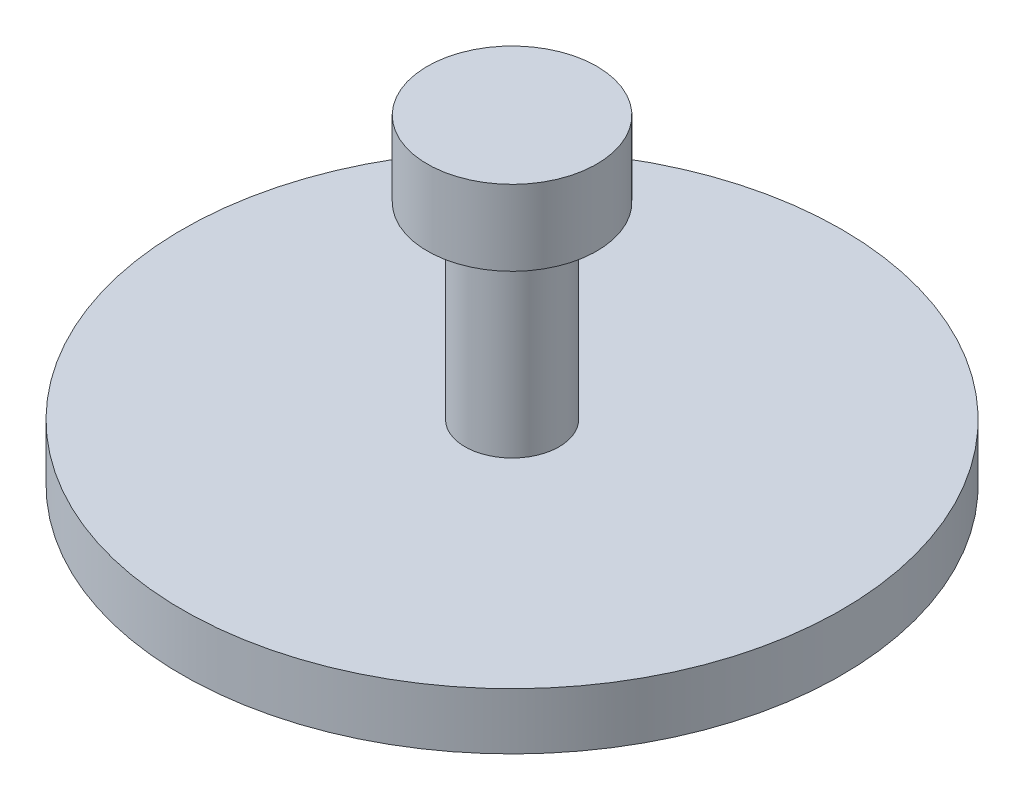
SolidWorks part; units mm, degrees
material "Plain Carbon Steel"
ref_plane "Front Plane" through (0, 0, 0) normal (0, 0, 1) x (1, 0, 0)
ref_plane "Top Plane" through (0, 0, 0) normal (0, 1, 0) x (1, 0, 0)
ref_plane "Right Plane" through (0, 0, 0) normal (1, 0, 0) x (0, 0, -1)
sketch "Sketch1" plane through (0, 0, 0) normal (0, 0, 1) x (1, 0, 0)
  line L0 (0, 0) -> (0, 17) construction
  line L1 (0, 0) -> (17.5, 0)
  line L2 (17.5, 0) -> (17.5, 3)
  line L3 (17.5, 3) -> (2.5, 3)
  line L4 (2.5, 3) -> (2.5, 13)
  line L5 (2.5, 13) -> (4.5, 13)
  line L6 (4.5, 13) -> (4.5, 17)
  line L7 (4.5, 17) -> (0, 17)
  line L8 (0, 17) -> (0, 0)
  dimension "D1" = 17.5
  dimension "D2" = 3
  dimension "D3" = 15
  dimension "D4" = 10
  dimension "D5" = 2
  dimension "D6" = 4
revolve "Revolve1" add sketch "Sketch1" angle 360 about L0
